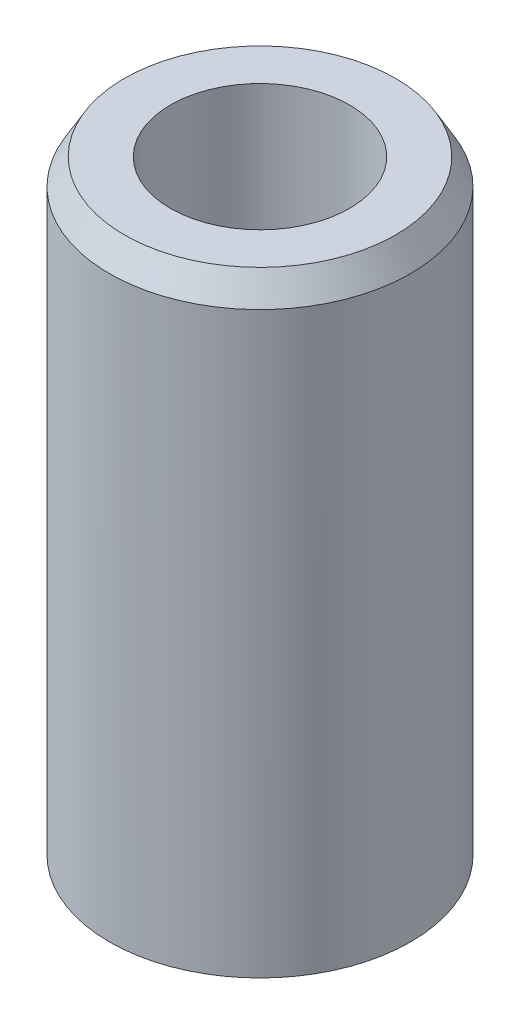
SolidWorks part; units mm, degrees
ref_plane "Front Plane" through (0, 0, 0) normal (0, 0, 1) x (1, 0, 0)
ref_plane "Top Plane" through (0, 0, 0) normal (0, 1, 0) x (1, 0, 0)
ref_plane "Right Plane" through (0, 0, 0) normal (1, 0, 0) x (0, 0, -1)
sketch "Sketch1" plane through (0, 0, 0) normal (0, 1, 0) x (1, 0, 0)
  circle A0 centre (0, 0) radius 22.5
  dimension "SHAFT_OD" = 45
extrude "Boss-Extrude1" add sketch "Sketch1" along normal blind 92.5887
sketch "Sketch2" plane through (0, 0, 0) normal (0, 1, 0) x (1, 0, 0)
  circle A0 centre (0, 0) radius 13.3878
  dimension "BORE_D" = 26.7756
extrude "Cut-Extrude1" cut sketch "Sketch2" along normal through all
chamfer "Chamfer1" distance 3.8808 angle 30 2 edges at (0, 92.5887, 22.5) (0, 0, 22.5) first distance on face at (0, 92.5887, 22.5) first distance on face at (0, 0, 13.3878)
